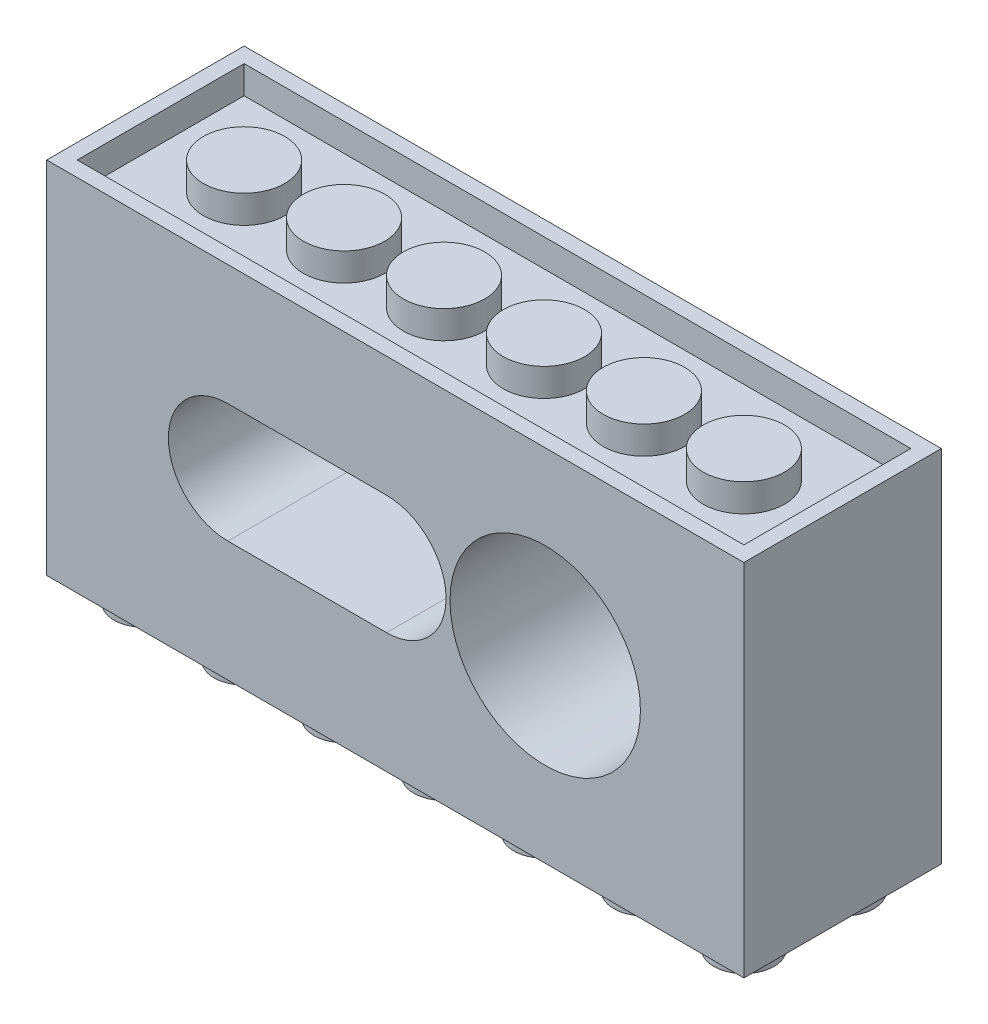
SolidWorks part; units mm, degrees
ref_plane "Front Plane" through (0, 0, 0) normal (0, 0, 1) x (1, 0, 0)
ref_plane "Top Plane" through (0, 0, 0) normal (0, 1, 0) x (1, 0, 0)
ref_plane "Right Plane" through (0, 0, 0) normal (1, 0, 0) x (0, 0, -1)
sketch "Sketch1" plane through (0, 0, 0) normal (0, 1, 0) x (1, 0, 0)
  line L1 (-39.0999, 16.0935) -> (16.7001, 16.0935)
  line L2 (-39.0999, 16.0935) -> (-39.0999, 0.2935)
  line L3 (-39.0999, 0.2935) -> (16.7001, 0.2935)
  line L4 (16.7001, 16.0935) -> (16.7001, 0.2935)
  dimension "D1" = 55.8
  dimension "D2" = 15.8
extrude "Boss-Extrude1" add sketch "Sketch1" along normal blind 28.8
sketch "Sketch2" plane through (0, 0, -0.2935) normal (0, 0, 1) x (1, 0, 0)
  line L0 (-39.0999, 0) -> (16.7001, 0) construction
  line L1 (-11.8999, 14.4) -> (-24.5999, 14.4) construction
  line L2 (-11.8999, 9.6375) -> (-24.5999, 9.6375)
  line L3 (-11.8999, 19.1625) -> (-24.5999, 19.1625)
  line L4 (16.7001, 28.8) -> (16.7001, 0) construction
  circle A0 centre (0.8001, 14.4) radius 7.62
  arc A1 (-11.8999, 9.6375) -> (-11.8999, 19.1625) centre (-11.8999, 14.4) ccw
  arc A2 (-24.5999, 19.1625) -> (-24.5999, 9.6375) centre (-24.5999, 14.4) ccw
  point P6 (-18.2499, 14.4)
  dimension "D4" = 15.24
  dimension "D5" = 4.7625
  dimension "D1" = 14.4
  dimension "D2" = 12.7
  dimension "D3" = 12.7
  dimension "D6" = 15.9
extrude "Cut-Extrude1" cut sketch "Sketch2" against normal blind 12.7
sketch "Sketch4" plane through (0, 0, -16.0935) normal (0, 0, -1) x (-1, 0, 0)
  line L0 (-16.7001, 28.8) -> (-16.7001, 0) construction
  circle A6 centre (-0.8001, 14.4) radius 2.7781
  circle A7 centre (11.8999, 14.4) radius 1.8415
  circle A8 centre (24.5999, 14.4) radius 1.8415
  dimension "D1" = 5.5563
  dimension "D2" = 3.683
  dimension "D3" = 3.683
  dimension "D4" = 12.7
  dimension "D5" = 12.7
  dimension "D6" = 15.9
extrude "Cut-Extrude2" cut sketch "Sketch4" against normal blind 12.7
sketch "Sketch5" plane through (0, 0, -16.0935) normal (0, 0, -1) x (-1, 0, 0)
  line L2 (24.5999, 19.1625) -> (11.8999, 19.1625)
  line L3 (11.8999, 9.6375) -> (24.5999, 9.6375)
  line L12 (24.5999, 19.1625) -> (11.8999, 19.1625)
  line L13 (11.8999, 9.6375) -> (24.5999, 9.6375)
  arc A2 (11.8999, 19.1625) -> (11.8999, 9.6375) centre (11.8999, 14.4) ccw
  arc A3 (24.5999, 9.6375) -> (24.5999, 19.1625) centre (24.5999, 14.4) ccw
  arc A4 (11.8999, 19.1625) -> (11.8999, 9.6375) centre (11.8999, 14.4) ccw
  arc A5 (24.5999, 9.6375) -> (24.5999, 19.1625) centre (24.5999, 14.4) ccw
  dimension "D2" = 0
extrude "Cut-Extrude6" cut sketch "Sketch5" against normal blind 1.905
sketch "Sketch8" plane through (0, 28.8, 0) normal (0, 1, 0) x (1, 0, 0)
  line L0 (-39.0999, 16.0935) -> (-39.0999, 0.2935) construction
  line L1 (-37.8799, 14.8735) -> (15.4801, 14.8735)
  line L2 (-37.8799, 14.8735) -> (-37.8799, 1.5135)
  line L3 (-37.8799, 1.5135) -> (15.4801, 1.5135)
  line L4 (15.4801, 14.8735) -> (15.4801, 1.5135)
  line L9 (16.7001, 16.0935) -> (-39.0999, 16.0935) construction
  line L10 (-39.0999, 0.2935) -> (16.7001, 0.2935) construction
  line L11 (16.7001, 0.2935) -> (16.7001, 16.0935) construction
  line L12 (-39.0999, 16.0935) -> (-39.0999, 0.2935) construction
  circle A0 centre (-31.1999, 8.1935) radius 3.26
  circle A1 centre (-23.1999, 8.1935) radius 3.26
  circle A2 centre (-15.1999, 8.1935) radius 3.26
  circle A3 centre (-7.1999, 8.1935) radius 3.26
  circle A4 centre (0.8001, 8.1935) radius 3.26
  circle A5 centre (8.8001, 8.1935) radius 3.26
  point P14 (-39.0999, 8.1935)
  dimension "D1" = 6.52
  dimension "D2" = 1.22
  dimension "D3" = 1.22
  dimension "D4" = 1.22
  dimension "D5" = 1.22
  dimension "D6" = 7.9
  dimension "D7" = 7.9
  dimension "D8" = 6
extrude "Cut-Extrude8" cut sketch "Sketch8" against normal blind 2.23
sketch "Sketch11" plane through (0, 0, 0) normal (0, -1, 0) x (1, 0, 0)
  line L1 (-39.0999, -0.2935) -> (16.7001, -0.2935) construction
  line L2 (-39.0999, -16.0935) -> (-39.0999, -0.2935) construction
  circle A0 centre (-35.1999, -4.1935) radius 2.405
  circle A1 centre (-35.1999, -12.1935) radius 2.405
  circle A2 centre (-27.1999, -4.1935) radius 2.405
  circle A3 centre (-27.1999, -12.1935) radius 2.405
  circle A4 centre (-19.1999, -4.1935) radius 2.405
  circle A5 centre (-19.1999, -12.1935) radius 2.405
  circle A6 centre (-11.1999, -4.1935) radius 2.405
  circle A7 centre (-11.1999, -12.1935) radius 2.405
  circle A8 centre (-3.1999, -4.1935) radius 2.405
  circle A9 centre (-3.1999, -12.1935) radius 2.405
  circle A10 centre (4.8001, -4.1935) radius 2.405
  circle A11 centre (4.8001, -12.1935) radius 2.405
  circle A12 centre (12.8001, -4.1935) radius 2.405
  circle A13 centre (12.8001, -12.1935) radius 2.405
  dimension "D1" = 4.81
  dimension "D2" = 4.81
  dimension "D3" = 8
  dimension "D4" = 3.9
  dimension "D5" = 3.9
  dimension "D6" = 3.9
  dimension "D7" = 7
extrude "Boss-Extrude3" add sketch "Sketch11" along normal blind 1.9
